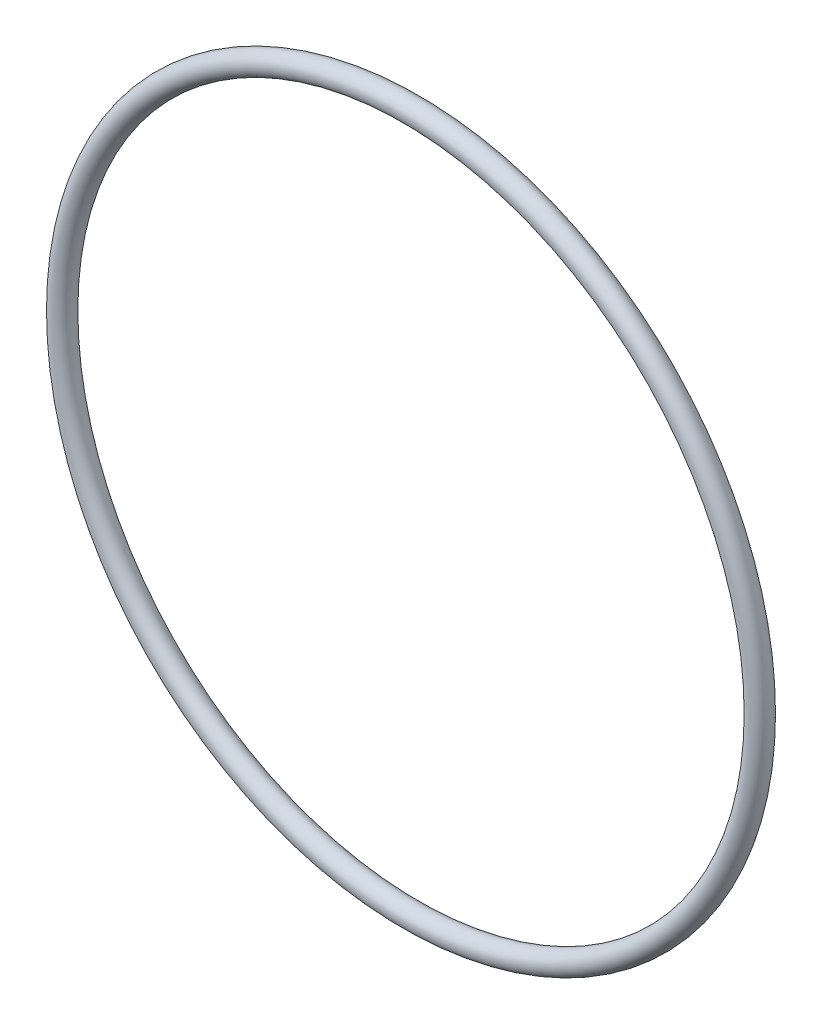
SolidWorks part; units mm, degrees
material "BUNA-N Rubber"
ref_plane "Front" through (0, 0, 0) normal (0, 0, 1) x (1, 0, 0)
ref_plane "Top" through (0, 0, 0) normal (0, 1, 0) x (1, 0, 0)
ref_plane "Right" through (0, 0, 0) normal (1, 0, 0) x (0, 0, -1)
sketch "Sketch1" plane through (0, 0, 0) normal (1, 0, 0) x (0, -1, 0)
  line L0 (0, -1.7653) -> (0, 1.7653) construction
  line L2 (-63.0326, 0) -> (63.0326, 0) construction
  line L3 (-53.7718, 0) -> (53.7718, 0) construction
  circle A0 centre (55.5371, 0) radius 1.7653
  point P9 (53.7718, 0)
  point P10 (57.3024, 0)
  point P13 (55.5371, 1.7653)
  point P14 (55.5371, -1.7653)
  dimension "Width" = 3.5306
  dimension "ID" = 107.5436
revolve "Revolve1" add sketch "Sketch1" angle 360 about L0
ref_axis "Axis1" through (0, 0, 1.9418) along (0, 0, -1)
